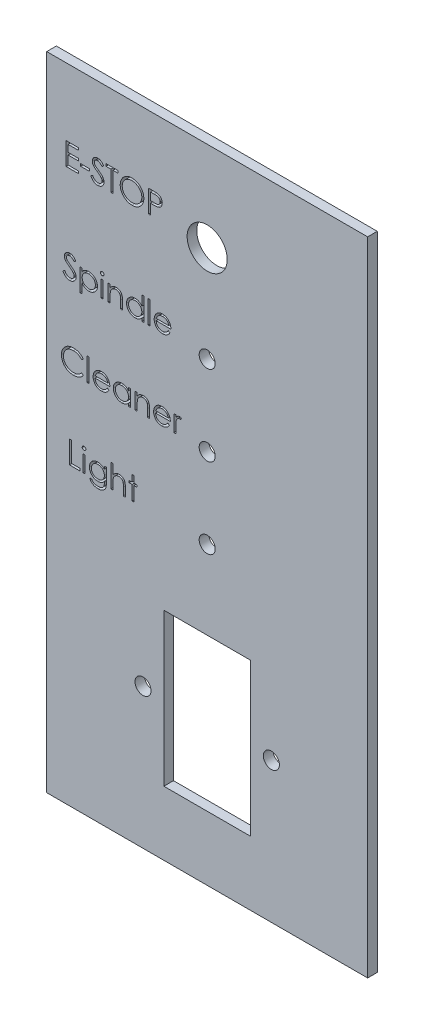
SolidWorks part; units mm, degrees
ref_plane "Front Plane" through (0, 0, 0) normal (0, 0, 1) x (1, 0, 0)
ref_plane "Top Plane" through (0, 0, 0) normal (0, 1, 0) x (1, 0, 0)
ref_plane "Right Plane" through (0, 0, 0) normal (1, 0, 0) x (0, 0, -1)
sketch "Sketch1" plane through (0, 0, 0) normal (0, 0, 1) x (1, 0, 0)
  line L1 (-50, -100) -> (50, -100)
  line L2 (-50, -100) -> (-50, 100)
  line L3 (-50, 100) -> (50, 100)
  line L4 (50, -100) -> (50, 100)
  line L5 (-50, -100) -> (50, 100) construction
  line L6 (-50, 100) -> (50, -100) construction
  point P0 (0, 0)
  dimension "D1" = 200
  dimension "D2" = 100
extrude "Boss-Extrude1" add sketch "Sketch1" along normal blind 3
sketch "Sketch2" plane through (0, 0, 3) normal (0, 0, 1) x (1, 0, 0)
  line L0 (-50, -100) -> (50, -100) construction
  line L5 (-13.5, -80) -> (13.5, -80)
  line L6 (-13.5, -80) -> (-13.5, -32.5)
  line L7 (-13.5, -32.5) -> (13.5, -32.5)
  line L8 (13.5, -80) -> (13.5, -32.5)
  line L9 (0, -1000) -> (0, 49000) construction
  circle A0 centre (20, -56.25) radius 2.5
  circle A1 centre (-20, -56.25) radius 2.5
  point P6 (0, -32.5)
  point P11 (13.5, -56.25)
  dimension "D4" = 20
  dimension "D5" = 5
  dimension "D1" = 47.5
  dimension "D2" = 27
  dimension "D3" = 20
extrude "Cut-Extrude1" cut sketch "Sketch2" against normal up to next
sketch "Sketch3" plane through (0, 0, 3) normal (0, 0, 1) x (1, 0, 0)
  line L0 (0, -1000) -> (0, 49000) construction
  line L1 (50, 100) -> (-50, 100) construction
  circle A0 centre (0, 72) radius 6.25
  circle A1 centre (0, 42) radius 2.5
  circle A2 centre (0, 17) radius 2.5
  circle A3 centre (0, -8) radius 2.5
  dimension "D1" = 12.5
  dimension "D3" = 5
  dimension "D5" = 25
  dimension "D6" = 25
  dimension "D2" = 28
  dimension "D4" = 30
extrude "Cut-Extrude2" cut sketch "Sketch3" against normal through all
sketch "Sketch4" plane through (0, 0, 3) normal (0, 0, 1) x (1, 0, 0)
  line L0 (0, 72) -> (-50, 72) construction
  line L1 (-50, 100) -> (-50, -100) construction
  line L2 (0, 42) -> (-50, 42) construction
  line L3 (0, 17) -> (-50, 17) construction
  line L4 (0, -8) -> (-50, -8) construction
  text T0 "E-STOP     " font "Century Gothic" height 7
  text T1 "Spindle    " font "Century Gothic" height 7
  text T2 "Cleaner   " font "Century Gothic" height 7
  text T3 "Light        " font "Century Gothic" height 7
extrude "Cut-Extrude3" cut sketch "Sketch4" against normal through all
